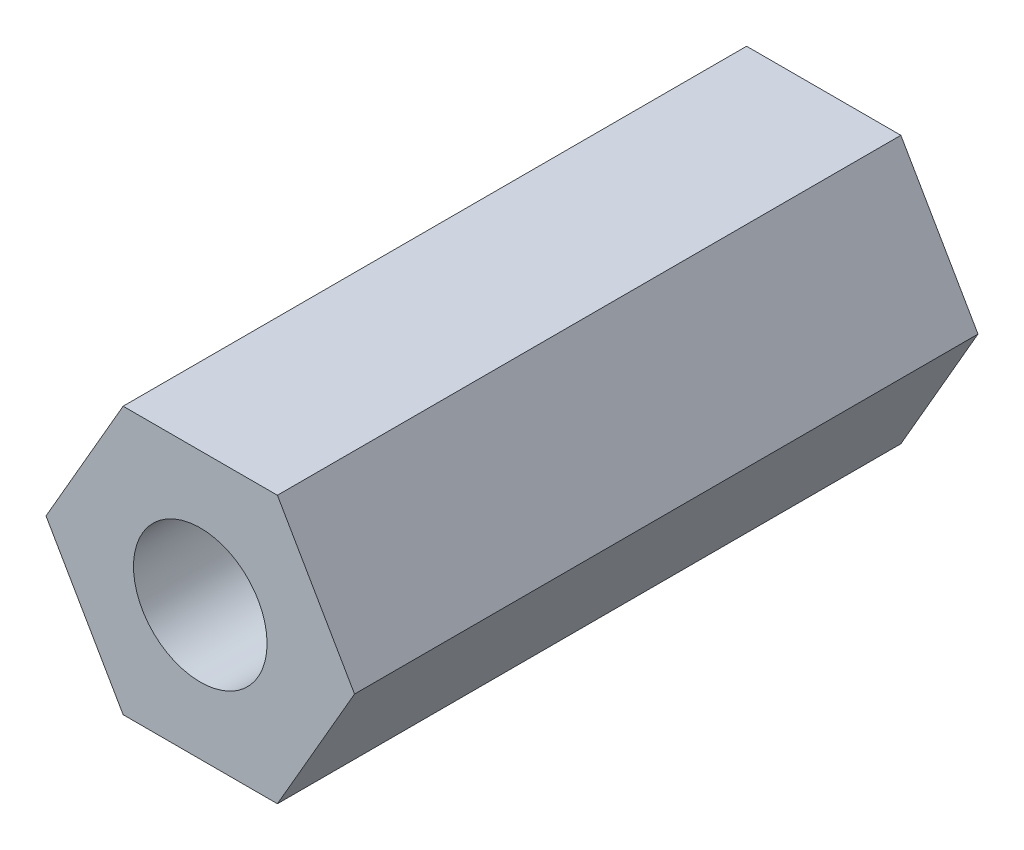
SolidWorks part; units mm, degrees
material "普通碳钢"
ref_plane "前视" through (0, 0, 0) normal (0, 0, 1) x (1, 0, 0)
ref_plane "上视" through (0, 0, 0) normal (0, 1, 0) x (1, 0, 0)
ref_plane "右视" through (0, 0, 0) normal (1, 0, 0) x (0, 0, -1)
sketch "草图1" plane through (0, 0, 0) normal (0, 0, 1) x (1, 0, 0)
  line L0 (0, 0) -> (3.4641, 0)
  line L1 (3.4641, 0) -> (5.1962, -3)
  line L2 (5.1962, -3) -> (3.4641, -6)
  line L3 (3.4641, -6) -> (0, -6)
  line L4 (0, -6) -> (-1.7321, -3)
  line L5 (-1.7321, -3) -> (0, 0)
  dimension "D1" = 6
  dimension "D2" = 6
extrude "凸台-拉伸1" add sketch "草图1" along normal blind 13
sketch "草图2" plane through (0, 0, 13) normal (0, 0, 1) x (1, 0, 0)
  line L0 (1.7321, 0) -> (1.7321, -6) construction
  line L1 (3.4641, 0) -> (0, 0) construction
  line L2 (0, -6) -> (3.4641, -6) construction
  line L3 (5.1962, -3) -> (-1.7321, -3) construction
  circle A0 centre (1.7321, -3) radius 1.5
extrude "切除-拉伸1" cut sketch "草图2" against normal through all
extrude "凸台-拉伸2" add sketch "草图1<2>" against normal blind 1
sketch "草图1<2>" plane through (0, 0, 0) normal (0, 0, 1) x (1, 0, 0) same geometry as "草图1"
extrude "切除-拉伸2" cut sketch "草图2<2>" against normal blind 15
sketch "草图2<2>" plane through (0, 0, 13) normal (0, 0, 1) x (1, 0, 0) same geometry as "草图2"
